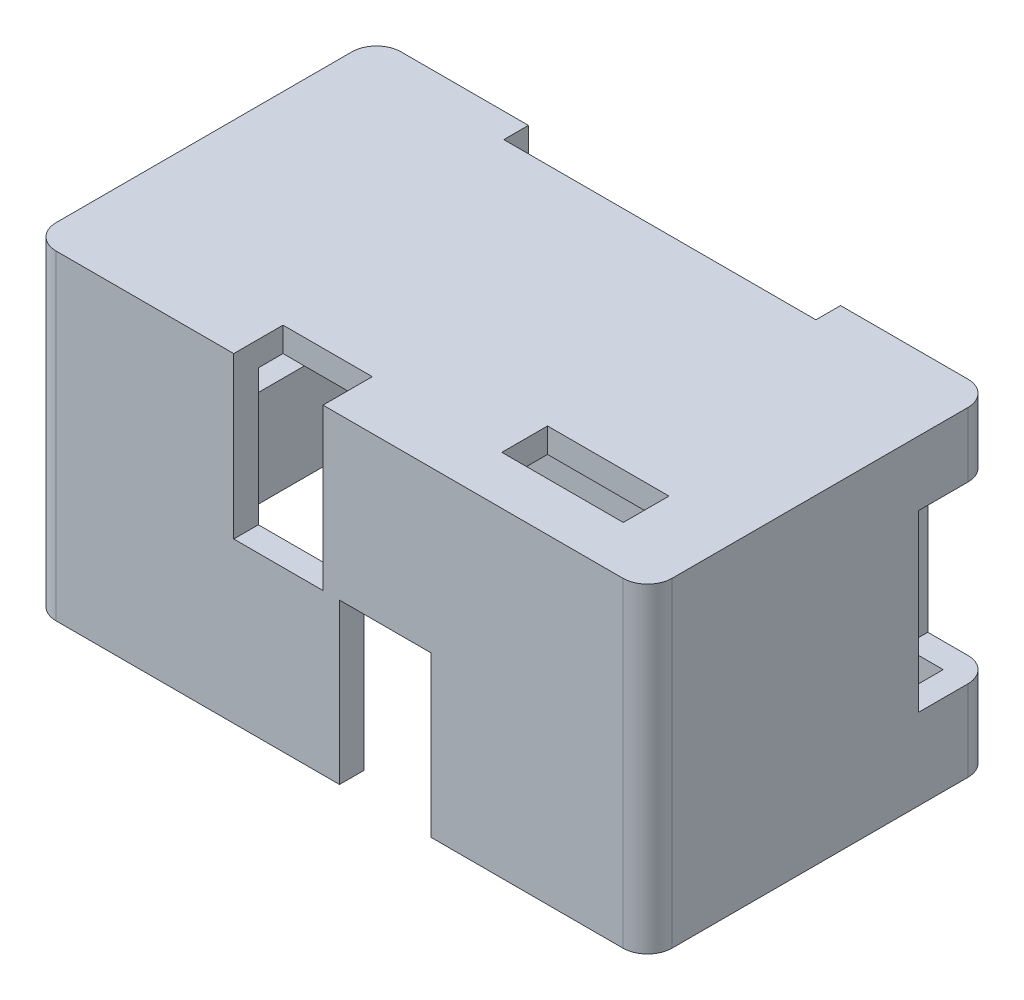
SolidWorks part; units mm, degrees
ref_plane "前视基准面" through (0, 0, 0) normal (0, 0, 1) x (1, 0, 0)
ref_plane "上视基准面" through (0, 0, 0) normal (0, 1, 0) x (1, 0, 0)
ref_plane "右视基准面" through (0, 0, 0) normal (1, 0, 0) x (0, 0, -1)
other "Configuration Table"
sketch "草图1" plane through (0, 0, 0) normal (0, 1, 0) x (1, 0, 0)
  line L1 (-41.7566, 26.6135) -> (73.2434, 26.6135)
  line L2 (-46.7566, 21.6135) -> (-46.7566, -38.3865)
  line L3 (-41.7566, -43.3865) -> (73.2434, -43.3865)
  line L4 (78.2434, 21.6135) -> (78.2434, -38.3865)
  arc A0 (73.2434, 26.6135) -> (78.2434, 21.6135) centre (73.2434, 21.6135) cw
  arc A1 (73.2434, -43.3865) -> (78.2434, -38.3865) centre (73.2434, -38.3865) ccw
  arc A2 (-46.7566, -38.3865) -> (-41.7566, -43.3865) centre (-41.7566, -38.3865) ccw
  arc A3 (-41.7566, 26.6135) -> (-46.7566, 21.6135) centre (-41.7566, 21.6135) ccw
  point P6 (78.2434, 26.6135)
  point P9 (78.2434, -43.3865)
  point P12 (-46.7566, -43.3865)
  point P15 (-46.7566, 26.6135)
  dimension "D4" = 5
  dimension "D1" = 125
  dimension "D2" = 70
  dimension "D3" = 70
extrude "凸台-拉伸1" [suppressed] add sketch "草图1" along normal blind 56 contours L2 A2 L3 A1 L4 A0 L1 A3
shell "抽壳2" [suppressed] thickness 5
sketch "草图5" plane through (0, 0, 0) normal (0, 0, 1) x (1, 0, 0)
extrude "凸台-拉伸5" add sketch "草图1<7>" along normal blind 65
sketch "草图1<7>" plane through (0, 0, 0) normal (0, 1, 0) x (1, 0, 0) same geometry as "草图1"
shell "抽壳8" thickness 5 removed face at (15.7434, 0, 8.3865)
sketch "草图7" plane through (0, 0, 43.3865) normal (0, 0, 1) x (1, 0, 0)
  line L0 (-41.7566, 0) -> (73.2434, 0) construction
  line L1 (15.7434, 0) -> (34.2882, 0)
  line L2 (15.7434, 0) -> (15.7434, 32.4141)
  line L3 (15.7434, 32.4141) -> (34.2882, 32.4141)
  line L4 (34.2882, 0) -> (34.2882, 32.4141)
extrude "切除-拉伸1" cut sketch "草图7" against normal blind 10
sketch "草图8" plane through (0, 0, 43.3865) normal (0, 0, 1) x (1, 0, 0)
  line L0 (-41.7566, 65) -> (73.2434, 65) construction
  line L1 (12.395, 32.4141) -> (-5.7205, 32.4141)
  line L2 (12.395, 32.4141) -> (12.395, 65)
  line L3 (12.395, 65) -> (-5.7205, 65)
  line L4 (-5.7205, 32.4141) -> (-5.7205, 65)
extrude "切除-拉伸2" cut sketch "草图8" against normal blind 10
sketch "草图9" plane through (0, 0, -26.6135) normal (0, 0, -1) x (-1, 0, 0)
  line L0 (-73.2434, 65) -> (41.7566, 65) construction
  line L1 (-47.4082, 38.7789) -> (15.9214, 38.7789)
  line L2 (-47.4082, 38.7789) -> (-47.4082, 91.2211)
  line L3 (-47.4082, 91.2211) -> (15.9214, 91.2211)
  line L4 (15.9214, 38.7789) -> (15.9214, 91.2211)
  line L5 (-47.4082, 38.7789) -> (15.9214, 91.2211) construction
  line L6 (-47.4082, 91.2211) -> (15.9214, 38.7789) construction
  point P0 (-15.7434, 65)
extrude "切除-拉伸3" cut sketch "草图9" against normal blind 5
sketch "草图10" plane through (0, 0, -26.6135) normal (0, 0, -1) x (-1, 0, 0)
  line L0 (-78.2434, 65) -> (-78.2434, 0) construction
  line L1 (-65.1104, 51.8894) -> (-78.2434, 51.8894)
  line L2 (-65.1104, 51.8894) -> (-65.1104, 16.445)
  line L3 (-65.1104, 16.445) -> (-78.2434, 16.445)
  line L4 (-78.2434, 51.8894) -> (-78.2434, 16.445)
extrude "切除-拉伸4" cut sketch "草图10" against normal blind 15
sketch "草图11" plane through (-46.7566, 0, 0) normal (-1, 0, 0) x (0, 0, 1)
  line L0 (38.3865, 65) -> (38.3865, 0) construction
  line L1 (-21.6135, 65) -> (-21.6135, 0) construction
  line L2 (38.3865, 39.6807) -> (-21.6135, 39.6807)
  line L3 (38.3865, 39.6807) -> (38.3865, 19.628)
  line L4 (38.3865, 19.628) -> (-21.6135, 19.628)
  line L5 (-21.6135, 39.6807) -> (-21.6135, 19.628)
extrude "切除-拉伸5" cut sketch "草图11" against normal blind 5
sketch "草图12" plane through (0, 65, 0) normal (0, 1, 0) x (1, 0, 0)
  line L1 (63.4792, -33.5422) -> (38.8386, -33.5422)
  line L2 (63.4792, -33.5422) -> (63.4792, -24.2698)
  line L3 (63.4792, -24.2698) -> (38.8386, -24.2698)
  line L4 (38.8386, -33.5422) -> (38.8386, -24.2698)
extrude "切除-拉伸6" cut sketch "草图12" against normal blind 5
